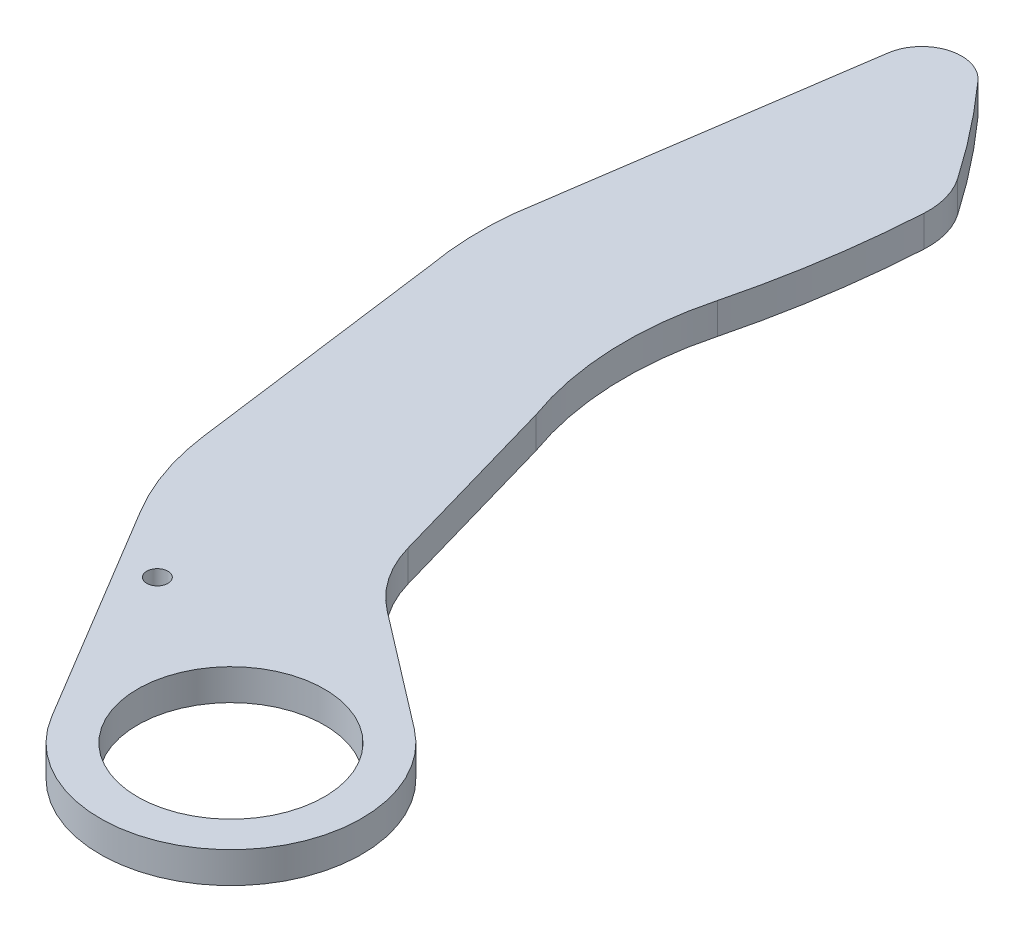
SolidWorks part; units mm, degrees
ref_plane "Front Plane" through (0, 0, 0) normal (0, 0, 1) x (1, 0, 0)
ref_plane "Top Plane" through (0, 0, 0) normal (0, 1, 0) x (1, 0, 0)
ref_plane "Right Plane" through (0, 0, 0) normal (1, 0, 0) x (0, 0, -1)
sketch "Sketch1" plane through (0, 0, 0) normal (0, 1, 0) x (1, 0, 0)
  line L42 (12.7669, 16.6735) -> (-5.8063, 30.895)
  line L43 (-12.8731, 41.2636) -> (-21.1395, 70.1022)
  line L44 (-43.1946, 148.7152) -> (-50.9327, 96.0562)
  line L45 (-50.3835, 82.3644) -> (-44.8249, 40.292)
  line L46 (-39.4657, 24.9456) -> (-18.0055, -10.8075)
  arc A148 (-22.4566, 100.5997) -> (-21.1395, 70.1022) centre (26.9938, 87.458) ccw
  arc A149 (-22.4566, 100.5997) -> (-18.0206, 129.2968) centre (-171.2572, 138.2924) ccw
  arc A150 (-18.0206, 129.2968) -> (-20.1164, 136.8055) centre (-30, 130) ccw
  arc A151 (-20.1164, 136.8055) -> (-32.0981, 152.0476) centre (-146.5445, 49.7519) ccw
  arc A152 (-32.0981, 152.0476) -> (-43.1946, 148.7152) centre (-36.8667, 147.7853) ccw
  arc A153 (-50.9327, 96.0562) -> (-50.3835, 82.3644) centre (0.0072, 91.2427) ccw
  circle A154 centre (0, 0) radius 15
  arc A155 (12.7669, 16.6735) -> (-18.0055, -10.8075) centre (0, 0) cw
  arc A156 (-5.8063, 30.895) -> (-12.8731, 41.2636) centre (6.3527, 46.7745) cw
  arc A157 (-44.8249, 40.292) -> (-39.4657, 24.9456) centre (-5.1695, 45.5313) ccw
  circle A158 centre (-28.9418, 17.1281) radius 1.7
  point P7 (-11.0524, 34.9119)
  point P11 (-43.7376, 32.0627)
  dimension "D3" = 12
  dimension "D4" = 30
  dimension "D5" = 6
  dimension "D8" = 20
  dimension "D10" = 40
  dimension "D11" = 3.4
  dimension "D1" = 130
  dimension "D2" = 30
  dimension "D6" = 50
  dimension "D7" = 30
  dimension "D9" = 30
  dimension "D12" = 5
  dimension "D13" = 30
extrude "Boss-Extrude2" add sketch "Sketch1" along normal blind 5
sketch "Sketch2" plane through (0, 5, 0) normal (0, 1, 0) x (1, 0, 0)
  line L0 (12.7669, 16.6735) -> (-5.8063, 30.895) construction
  point P0 (11.1334, 17.9243)
